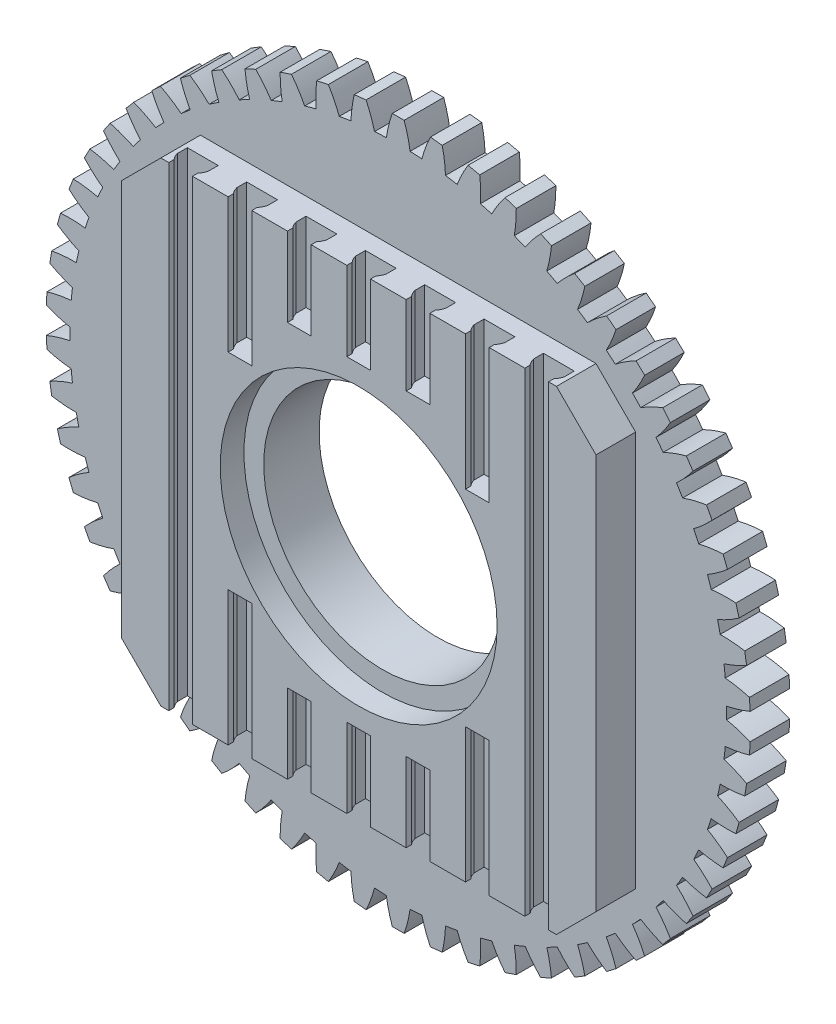
SolidWorks part; units mm, degrees
ref_plane "前视基准面" through (0, 0, 0) normal (0, 0, 1) x (1, 0, 0)
ref_plane "上视基准面" through (0, 0, 0) normal (0, 1, 0) x (1, 0, 0)
ref_plane "右视基准面" through (0, 0, 0) normal (1, 0, 0) x (0, 0, -1)
sketch "草图1" plane through (0, 0, 0) normal (0, 0, 1) x (1, 0, 0)
  circle A0 centre (0, 0) radius 41.5
extrude "凸台-拉伸1" add sketch "草图1" against normal blind 5
sketch "草图2" plane through (0, 0, 0) normal (0, 0, 1) x (1, 0, 0)
  line L1 (-30, 30) -> (30, 30)
  line L2 (-30, 30) -> (-30, -30)
  line L3 (-30, -30) -> (30, -30)
  line L4 (30, 30) -> (30, -30)
extrude "凸台-拉伸2" add sketch "草图2" along normal blind 5
sketch "草图3" plane through (0, -30, 0) normal (0, -1, 0) x (1, 0, 0)
  line L0 (-30, 5) -> (30, 5) construction
  line L1 (-1.5, 5) -> (1.5, 5)
  line L2 (-1.5, 5) -> (-1.5, 4.3229)
  line L3 (6, 5) -> (6, 4.3229)
  line L4 (1.5, 5) -> (1.5, 4.3229)
  line L5 (-1.95, 2.2) -> (1.95, 2.2)
  line L6 (-1.95, 2.2) -> (-1.95, 3.4444)
  line L7 (1.95, 2.2) -> (1.95, 3.4444)
  line L8 (9.45, 2.2) -> (9.45, 3.4444)
  line L9 (9, 5) -> (9, 4.3229)
  line L10 (6, 5) -> (9, 5)
  line L11 (5.55, 2.2) -> (9.45, 2.2)
  line L12 (5.55, 2.2) -> (5.55, 3.4444)
  line L13 (-9, 5) -> (-9, 4.3229)
  line L14 (-5.55, 2.2) -> (-5.55, 3.4444)
  line L15 (-6, 5) -> (-6, 4.3229)
  line L16 (-9, 5) -> (-6, 5)
  line L17 (-9.45, 2.2) -> (-5.55, 2.2)
  line L18 (-9.45, 2.2) -> (-9.45, 3.4444)
  arc A0 (6, 4.3229) -> (5.55, 3.4444) centre (7.5, 3) ccw
  arc A1 (-1.5, 4.3229) -> (-1.95, 3.4444) centre (0, 3) ccw
  arc A2 (1.95, 3.4444) -> (1.5, 4.3229) centre (0, 3) ccw
  arc A3 (9.45, 3.4444) -> (9, 4.3229) centre (7.5, 3) ccw
  arc A4 (-9, 4.3229) -> (-9.45, 3.4444) centre (-7.5, 3) ccw
  arc A5 (-5.55, 3.4444) -> (-6, 4.3229) centre (-7.5, 3) ccw
extrude "切除-拉伸1" cut sketch "草图3" against normal blind 10
extrude "切除-拉伸2" cut sketch "草图3<2>" along normal blind 10 from offset 60 offset against normal yes
sketch "草图3<2>" plane through (0, -30, 0) normal (0, -1, 0) x (1, 0, 0) same geometry as "草图3"
sketch "草图4" plane through (0, -30, 0) normal (0, -1, 0) x (1, 0, 0)
  line L0 (-16.5, 5) -> (-13.5, 5)
  line L3 (-16.5, 5) -> (-16.5, 4.3229)
  line L7 (-16.95, 2.2) -> (-13.05, 2.2)
  line L9 (-13.5, 5) -> (-13.5, 4.3229)
  line L10 (-16.95, 2.2) -> (-16.95, 3.4444)
  line L11 (-13.05, 2.2) -> (-13.05, 3.4444)
  line L12 (13.5, 5) -> (16.5, 5)
  line L13 (13.5, 5) -> (13.5, 4.3229)
  line L14 (13.05, 2.2) -> (16.95, 2.2)
  line L15 (16.5, 5) -> (16.5, 4.3229)
  line L16 (13.05, 2.2) -> (13.05, 3.4444)
  line L17 (16.95, 2.2) -> (16.95, 3.4444)
  arc A2 (-16.5, 4.3229) -> (-16.95, 3.4444) centre (-15, 3) ccw
  arc A3 (-13.05, 3.4444) -> (-13.5, 4.3229) centre (-15, 3) ccw
  arc A4 (13.5, 4.3229) -> (13.05, 3.4444) centre (15, 3) ccw
  arc A5 (16.95, 3.4444) -> (16.5, 4.3229) centre (15, 3) ccw
extrude "切除-拉伸3" cut sketch "草图4" against normal blind 17
extrude "切除-拉伸4" cut sketch "草图4<2>" along normal blind 17 from offset 60 offset against normal yes
sketch "草图4<2>" plane through (0, -30, 0) normal (0, -1, 0) x (1, 0, 0) same geometry as "草图4"
sketch "草图5" plane through (0, -30, 0) normal (0, -1, 0) x (1, 0, 0)
  line L0 (-21, 5) -> (-21, 4.3229)
  line L3 (-24, 5) -> (-21, 5)
  line L7 (-24.45, 2.2) -> (-20.55, 2.2)
  line L9 (-20.55, 2.2) -> (-20.55, 3.4444)
  line L10 (-24.45, 2.2) -> (-24.45, 3.4444)
  line L11 (-24, 5) -> (-24, 4.3229)
  line L12 (24, 5) -> (24, 4.3229)
  line L13 (21, 5) -> (24, 5)
  line L14 (20.55, 2.2) -> (24.45, 2.2)
  line L15 (24.45, 2.2) -> (24.45, 3.4444)
  line L16 (20.55, 2.2) -> (20.55, 3.4444)
  line L17 (21, 5) -> (21, 4.3229)
  arc A2 (-24, 4.3229) -> (-24.45, 3.4444) centre (-22.5, 3) ccw
  arc A3 (-20.55, 3.4444) -> (-21, 4.3229) centre (-22.5, 3) ccw
  arc A4 (21, 4.3229) -> (20.55, 3.4444) centre (22.5, 3) ccw
  arc A5 (24.45, 3.4444) -> (24, 4.3229) centre (22.5, 3) ccw
extrude "切除-拉伸5" cut sketch "草图5" against normal up to next
chamfer "倒角1" distance 5 angle 45 4 edges at (-30, 30, 2.5) (30, 30, 2.5) (30, -30, 2.5) (-30, -30, 2.5)
sketch "草图6" plane through (0, 0, 5) normal (0, 0, 1) x (1, 0, 0)
  circle A0 centre (0, 0) radius 17.5
extrude "切除-拉伸6" cut sketch "草图6" against normal blind 3
sketch "草图7" plane through (0, 0, 2) normal (0, 0, 1) x (1, 0, 0)
  circle A0 centre (0, 0) radius 15
extrude "切除-拉伸7" cut sketch "草图7" against normal through all
sketch "草图9" plane through (0, 0, -5) normal (0, 0, -1) x (-1, 0, 0)
  circle A0 centre (0, 0) radius 19
  circle A1 centre (0, 0) radius 39.5
extrude "切除-拉伸8" cut sketch "草图9" against normal blind 3
sketch "草图8" plane through (0, 0, -5) normal (0, 0, -1) x (-1, 0, 0)
  line L0 (5.5569, 44.158) -> (4.0657, 44.3202)
  line L1 (10.2987, 43.2984) -> (8.8337, 43.6208)
  line L2 (14.9197, 41.9311) -> (13.4982, 42.41)
  line L3 (0.75, 44.5) -> (-0.75, 44.5)
  line L4 (19.3657, 40.0722) -> (18.0044, 40.702)
  line L5 (23.5848, 37.7435) -> (22.2995, 38.5168)
  line L6 (27.5273, 34.9723) -> (26.3332, 35.88)
  line L7 (31.1471, 31.791) -> (30.0581, 32.8226)
  line L8 (34.4018, 28.2371) -> (33.4307, 29.3803)
  line L9 (37.2531, 24.3521) -> (36.4113, 25.5936)
  line L10 (39.6676, 20.1815) -> (38.965, 21.5068)
  line L11 (41.6171, 15.7744) -> (41.0619, 17.1679)
  line L12 (43.0786, 11.1823) -> (42.6773, 12.6277)
  line L13 (44.0351, 6.4592) -> (43.7924, 7.9394)
  line L14 (44.4753, 1.6603) -> (44.3941, 3.1581)
  line L15 (44.3941, -3.1581) -> (44.4753, -1.6603)
  line L16 (43.7924, -7.9394) -> (44.0351, -6.4592)
  line L17 (42.6773, -12.6277) -> (43.0786, -11.1823)
  line L18 (41.0619, -17.1679) -> (41.6171, -15.7744)
  line L19 (38.965, -21.5068) -> (39.6676, -20.1815)
  line L20 (36.4113, -25.5936) -> (37.2531, -24.3521)
  line L21 (33.4307, -29.3803) -> (34.4018, -28.2371)
  line L22 (30.0581, -32.8226) -> (31.1471, -31.791)
  line L23 (26.3332, -35.88) -> (27.5273, -34.9723)
  line L24 (22.2995, -38.5168) -> (23.5848, -37.7435)
  line L25 (18.0044, -40.702) -> (19.3657, -40.0722)
  line L26 (13.4982, -42.41) -> (14.9197, -41.9311)
  line L27 (8.8337, -43.6208) -> (10.2987, -43.2984)
  line L28 (4.0657, -44.3202) -> (5.5569, -44.158)
  line L29 (-0.75, -44.5) -> (0.75, -44.5)
  line L30 (-5.5569, -44.158) -> (-4.0657, -44.3202)
  line L31 (-10.2987, -43.2984) -> (-8.8337, -43.6208)
  line L32 (-14.9197, -41.9311) -> (-13.4982, -42.41)
  line L33 (-19.3657, -40.0722) -> (-18.0044, -40.702)
  line L34 (-23.5848, -37.7435) -> (-22.2995, -38.5168)
  line L35 (-27.5273, -34.9723) -> (-26.3332, -35.88)
  line L36 (-31.1471, -31.791) -> (-30.0581, -32.8226)
  line L37 (-34.4018, -28.2371) -> (-33.4307, -29.3803)
  line L38 (-37.2531, -24.3521) -> (-36.4113, -25.5936)
  line L39 (-39.6676, -20.1815) -> (-38.965, -21.5068)
  line L40 (-41.6171, -15.7744) -> (-41.0619, -17.1679)
  line L41 (-43.0786, -11.1823) -> (-42.6773, -12.6277)
  line L42 (-44.0351, -6.4592) -> (-43.7924, -7.9394)
  line L43 (-44.4753, -1.6603) -> (-44.3941, -3.1581)
  line L44 (-44.3941, 3.1581) -> (-44.4753, 1.6603)
  line L45 (-43.7924, 7.9394) -> (-44.0351, 6.4592)
  line L46 (-42.6773, 12.6277) -> (-43.0786, 11.1823)
  line L47 (-41.0619, 17.1679) -> (-41.6171, 15.7744)
  line L48 (-38.965, 21.5068) -> (-39.6676, 20.1815)
  line L49 (-36.4113, 25.5936) -> (-37.2531, 24.3521)
  line L50 (-33.4307, 29.3803) -> (-34.4018, 28.2371)
  line L51 (-30.0581, 32.8226) -> (-31.1471, 31.791)
  line L52 (-26.3332, 35.88) -> (-27.5273, 34.9723)
  line L53 (-22.2995, 38.5168) -> (-23.5848, 37.7435)
  line L54 (-18.0044, 40.702) -> (-19.3657, 40.0722)
  line L55 (-13.4982, 42.41) -> (-14.9197, 41.9311)
  line L56 (-8.8337, 43.6208) -> (-10.2987, 43.2984)
  line L57 (-4.0657, 44.3202) -> (-5.5569, 44.158)
  arc A0 (1.5, 41.4729) -> (-1.5, 41.4729) centre (0, 0) ccw
  arc A1 (-0.75, 44.5) -> (-1.5, 41.4729) centre (14.3529, 39.1516) ccw
  arc A2 (5.9752, 41.0676) -> (2.9928, 41.3919) centre (0, 0) ccw
  arc A3 (0.75, 44.5) -> (1.5, 41.4729) centre (-14.3529, 39.1516) cw
  arc A4 (4.0657, 44.3202) -> (2.9928, 41.3919) centre (18.5018, 37.3703) ccw
  arc A5 (5.5569, 44.158) -> (5.9752, 41.0676) centre (-10.0357, 40.4739) cw
  arc A6 (10.3804, 40.1808) -> (7.4505, 40.8257) centre (0, 0) ccw
  arc A7 (8.8337, 43.6208) -> (7.4505, 40.8257) centre (22.4338, 35.1508) ccw
  arc A8 (10.2987, 43.2984) -> (10.3804, 40.1808) centre (-5.6009, 41.3217) cw
  arc A9 (14.6638, 38.823) -> (11.8209, 39.7809) centre (0, 0) ccw
  arc A10 (13.4982, 42.41) -> (11.8209, 39.7809) centre (26.1028, 32.5193) ccw
  arc A11 (14.9197, 41.9311) -> (14.6638, 38.823) centre (-1.1004, 41.6851) cw
  arc A12 (18.7754, 37.0099) -> (16.0526, 38.2696) centre (0, 0) ccw
  arc A13 (18.0044, 40.702) -> (16.0526, 38.2696) centre (29.4657, 29.5064) ccw
  arc A14 (19.3657, 40.0722) -> (18.7754, 37.0099) centre (3.413, 41.5597) cw
  arc A15 (22.6668, 34.763) -> (20.0962, 36.3097) centre (0, 0) ccw
  arc A16 (22.2995, 38.5168) -> (20.0962, 36.3097) centre (32.4832, 26.1477) ccw
  arc A17 (23.5848, 37.7435) -> (22.6668, 34.763) centre (7.8864, 40.9471) cw
  arc A18 (26.2925, 32.1085) -> (23.9042, 33.924) centre (0, 0) ccw
  arc A19 (26.3332, 35.88) -> (23.9042, 33.924) centre (35.1198, 22.4823) ccw
  arc A20 (27.5273, 34.9723) -> (26.2925, 32.1085) centre (12.2673, 39.8543) cw
  arc A21 (29.6099, 29.0776) -> (27.4319, 31.1407) centre (0, 0) ccw
  arc A22 (30.0581, 32.8226) -> (27.4319, 31.1407) centre (37.3447, 18.5534) ccw
  arc A23 (31.1471, 31.791) -> (29.6099, 29.0776) centre (16.5044, 38.2944) cw
  arc A24 (32.5801, 25.7057) -> (30.638, 27.9922) centre (0, 0) ccw
  arc A25 (33.4307, 29.3803) -> (30.638, 27.9922) centre (39.1318, 14.407) ccw
  arc A26 (34.4018, 28.2371) -> (32.5801, 25.7057) centre (20.548, 36.2855) cw
  arc A27 (35.1684, 22.0325) -> (33.4849, 24.5156) centre (0, 0) ccw
  arc A28 (36.4113, 25.5936) -> (33.4849, 24.5156) centre (40.46, 10.0916) ccw
  arc A29 (37.2531, 24.3521) -> (35.1684, 22.0325) centre (24.3507, 33.8511) cw
  arc A30 (37.3444, 18.101) -> (35.9392, 20.7515) centre (0, 0) ccw
  arc A31 (38.965, 21.5068) -> (35.9392, 20.7515) centre (41.314, 5.658) ccw
  arc A32 (39.6676, 20.1815) -> (37.3444, 18.101) centre (27.8679, 31.0199) cw
  arc A33 (39.0825, 13.9572) -> (37.9721, 16.7442) centre (0, 0) ccw
  arc A34 (41.0619, 17.1679) -> (37.9721, 16.7442) centre (41.6835, 1.158) ccw
  arc A35 (41.6171, 15.7744) -> (39.0825, 13.9572) centre (31.0584, 27.825) cw
  arc A36 (40.3625, 9.6498) -> (39.5599, 12.5405) centre (0, 0) ccw
  arc A37 (42.6773, 12.6277) -> (39.5599, 12.5405) centre (41.5644, -3.3556) ccw
  arc A38 (43.0786, 11.1823) -> (40.3625, 9.6498) centre (33.8847, 24.3039) cw
  arc A39 (41.1692, 5.2293) -> (40.6839, 8.1898) centre (0, 0) ccw
  arc A40 (43.7924, 7.9394) -> (40.6839, 8.1898) centre (40.9579, -7.8298) ccw
  arc A41 (44.0351, 6.4592) -> (41.1692, 5.2293) centre (36.3138, 20.4979) cw
  arc A42 (41.4933, 0.7475) -> (41.3309, 3.7431) centre (0, 0) ccw
  arc A43 (44.3941, 3.1581) -> (41.3309, 3.7431) centre (39.8713, -12.2122) ccw
  arc A44 (44.4753, 1.6603) -> (41.4933, 0.7475) centre (38.3172, 16.4515) cw
  arc A45 (41.3309, -3.7431) -> (41.4933, -0.7475) centre (0, 0) ccw
  arc A46 (44.4753, -1.6603) -> (41.4933, -0.7475) centre (38.3172, -16.4515) ccw
  arc A47 (44.3941, -3.1581) -> (41.3309, -3.7431) centre (39.8713, 12.2122) cw
  arc A48 (40.6839, -8.1898) -> (41.1692, -5.2293) centre (0, 0) ccw
  arc A49 (44.0351, -6.4592) -> (41.1692, -5.2293) centre (36.3138, -20.4979) ccw
  arc A50 (43.7924, -7.9394) -> (40.6839, -8.1898) centre (40.9579, 7.8298) cw
  arc A51 (39.5599, -12.5405) -> (40.3625, -9.6498) centre (0, 0) ccw
  arc A52 (43.0786, -11.1823) -> (40.3625, -9.6498) centre (33.8847, -24.3039) ccw
  arc A53 (42.6773, -12.6277) -> (39.5599, -12.5405) centre (41.5644, 3.3556) cw
  arc A54 (37.9721, -16.7442) -> (39.0825, -13.9572) centre (0, 0) ccw
  arc A55 (41.6171, -15.7744) -> (39.0825, -13.9572) centre (31.0584, -27.825) ccw
  arc A56 (41.0619, -17.1679) -> (37.9721, -16.7442) centre (41.6835, -1.158) cw
  arc A57 (35.9392, -20.7515) -> (37.3444, -18.101) centre (0, 0) ccw
  arc A58 (39.6676, -20.1815) -> (37.3444, -18.101) centre (27.8679, -31.0199) ccw
  arc A59 (38.965, -21.5068) -> (35.9392, -20.7515) centre (41.314, -5.658) cw
  arc A60 (33.4849, -24.5156) -> (35.1684, -22.0325) centre (0, 0) ccw
  arc A61 (37.2531, -24.3521) -> (35.1684, -22.0325) centre (24.3507, -33.8511) ccw
  arc A62 (36.4113, -25.5936) -> (33.4849, -24.5156) centre (40.46, -10.0916) cw
  arc A63 (30.638, -27.9922) -> (32.5801, -25.7057) centre (0, 0) ccw
  arc A64 (34.4018, -28.2371) -> (32.5801, -25.7057) centre (20.548, -36.2855) ccw
  arc A65 (33.4307, -29.3803) -> (30.638, -27.9922) centre (39.1318, -14.407) cw
  arc A66 (27.4319, -31.1407) -> (29.6099, -29.0776) centre (0, 0) ccw
  arc A67 (31.1471, -31.791) -> (29.6099, -29.0776) centre (16.5044, -38.2944) ccw
  arc A68 (30.0581, -32.8226) -> (27.4319, -31.1407) centre (37.3447, -18.5534) cw
  arc A69 (23.9042, -33.924) -> (26.2925, -32.1085) centre (0, 0) ccw
  arc A70 (27.5273, -34.9723) -> (26.2925, -32.1085) centre (12.2673, -39.8543) ccw
  arc A71 (26.3332, -35.88) -> (23.9042, -33.924) centre (35.1198, -22.4823) cw
  arc A72 (20.0962, -36.3097) -> (22.6668, -34.763) centre (0, 0) ccw
  arc A73 (23.5848, -37.7435) -> (22.6668, -34.763) centre (7.8864, -40.9471) ccw
  arc A74 (22.2995, -38.5168) -> (20.0962, -36.3097) centre (32.4832, -26.1477) cw
  arc A75 (16.0526, -38.2696) -> (18.7754, -37.0099) centre (0, 0) ccw
  arc A76 (19.3657, -40.0722) -> (18.7754, -37.0099) centre (3.413, -41.5597) ccw
  arc A77 (18.0044, -40.702) -> (16.0526, -38.2696) centre (29.4657, -29.5064) cw
  arc A78 (11.8209, -39.7809) -> (14.6638, -38.823) centre (0, 0) ccw
  arc A79 (14.9197, -41.9311) -> (14.6638, -38.823) centre (-1.1004, -41.6851) ccw
  arc A80 (13.4982, -42.41) -> (11.8209, -39.7809) centre (26.1028, -32.5193) cw
  arc A81 (7.4505, -40.8257) -> (10.3804, -40.1808) centre (0, 0) ccw
  arc A82 (10.2987, -43.2984) -> (10.3804, -40.1808) centre (-5.6009, -41.3217) ccw
  arc A83 (8.8337, -43.6208) -> (7.4505, -40.8257) centre (22.4338, -35.1508) cw
  arc A84 (2.9928, -41.3919) -> (5.9752, -41.0676) centre (0, 0) ccw
  arc A85 (5.5569, -44.158) -> (5.9752, -41.0676) centre (-10.0357, -40.4739) ccw
  arc A86 (4.0657, -44.3202) -> (2.9928, -41.3919) centre (18.5018, -37.3703) cw
  arc A87 (-1.5, -41.4729) -> (1.5, -41.4729) centre (0, 0) ccw
  arc A88 (0.75, -44.5) -> (1.5, -41.4729) centre (-14.3529, -39.1516) ccw
  arc A89 (-0.75, -44.5) -> (-1.5, -41.4729) centre (14.3529, -39.1516) cw
  arc A90 (-5.9752, -41.0676) -> (-2.9928, -41.3919) centre (0, 0) ccw
  arc A91 (-4.0657, -44.3202) -> (-2.9928, -41.3919) centre (-18.5018, -37.3703) ccw
  arc A92 (-5.5569, -44.158) -> (-5.9752, -41.0676) centre (10.0357, -40.4739) cw
  arc A93 (-10.3804, -40.1808) -> (-7.4505, -40.8257) centre (0, 0) ccw
  arc A94 (-8.8337, -43.6208) -> (-7.4505, -40.8257) centre (-22.4338, -35.1508) ccw
  arc A95 (-10.2987, -43.2984) -> (-10.3804, -40.1808) centre (5.6009, -41.3217) cw
  arc A96 (-14.6638, -38.823) -> (-11.8209, -39.7809) centre (0, 0) ccw
  arc A97 (-13.4982, -42.41) -> (-11.8209, -39.7809) centre (-26.1028, -32.5193) ccw
  arc A98 (-14.9197, -41.9311) -> (-14.6638, -38.823) centre (1.1004, -41.6851) cw
  arc A99 (-18.7754, -37.0099) -> (-16.0526, -38.2696) centre (0, 0) ccw
  arc A100 (-18.0044, -40.702) -> (-16.0526, -38.2696) centre (-29.4657, -29.5064) ccw
  arc A101 (-19.3657, -40.0722) -> (-18.7754, -37.0099) centre (-3.413, -41.5597) cw
  arc A102 (-22.6668, -34.763) -> (-20.0962, -36.3097) centre (0, 0) ccw
  arc A103 (-22.2995, -38.5168) -> (-20.0962, -36.3097) centre (-32.4832, -26.1477) ccw
  arc A104 (-23.5848, -37.7435) -> (-22.6668, -34.763) centre (-7.8864, -40.9471) cw
  arc A105 (-26.2925, -32.1085) -> (-23.9042, -33.924) centre (0, 0) ccw
  arc A106 (-26.3332, -35.88) -> (-23.9042, -33.924) centre (-35.1198, -22.4823) ccw
  arc A107 (-27.5273, -34.9723) -> (-26.2925, -32.1085) centre (-12.2673, -39.8543) cw
  arc A108 (-29.6099, -29.0776) -> (-27.4319, -31.1407) centre (0, 0) ccw
  arc A109 (-30.0581, -32.8226) -> (-27.4319, -31.1407) centre (-37.3447, -18.5534) ccw
  arc A110 (-31.1471, -31.791) -> (-29.6099, -29.0776) centre (-16.5044, -38.2944) cw
  arc A111 (-32.5801, -25.7057) -> (-30.638, -27.9922) centre (0, 0) ccw
  arc A112 (-33.4307, -29.3803) -> (-30.638, -27.9922) centre (-39.1318, -14.407) ccw
  arc A113 (-34.4018, -28.2371) -> (-32.5801, -25.7057) centre (-20.548, -36.2855) cw
  arc A114 (-35.1684, -22.0325) -> (-33.4849, -24.5156) centre (0, 0) ccw
  arc A115 (-36.4113, -25.5936) -> (-33.4849, -24.5156) centre (-40.46, -10.0916) ccw
  arc A116 (-37.2531, -24.3521) -> (-35.1684, -22.0325) centre (-24.3507, -33.8511) cw
  arc A117 (-37.3444, -18.101) -> (-35.9392, -20.7515) centre (0, 0) ccw
  arc A118 (-38.965, -21.5068) -> (-35.9392, -20.7515) centre (-41.314, -5.658) ccw
  arc A119 (-39.6676, -20.1815) -> (-37.3444, -18.101) centre (-27.8679, -31.0199) cw
  arc A120 (-39.0825, -13.9572) -> (-37.9721, -16.7442) centre (0, 0) ccw
  arc A121 (-41.0619, -17.1679) -> (-37.9721, -16.7442) centre (-41.6835, -1.158) ccw
  arc A122 (-41.6171, -15.7744) -> (-39.0825, -13.9572) centre (-31.0584, -27.825) cw
  arc A123 (-40.3625, -9.6498) -> (-39.5599, -12.5405) centre (0, 0) ccw
  arc A124 (-42.6773, -12.6277) -> (-39.5599, -12.5405) centre (-41.5644, 3.3556) ccw
  arc A125 (-43.0786, -11.1823) -> (-40.3625, -9.6498) centre (-33.8847, -24.3039) cw
  arc A126 (-41.1692, -5.2293) -> (-40.6839, -8.1898) centre (0, 0) ccw
  arc A127 (-43.7924, -7.9394) -> (-40.6839, -8.1898) centre (-40.9579, 7.8298) ccw
  arc A128 (-44.0351, -6.4592) -> (-41.1692, -5.2293) centre (-36.3138, -20.4979) cw
  arc A129 (-41.4933, -0.7475) -> (-41.3309, -3.7431) centre (0, 0) ccw
  arc A130 (-44.3941, -3.1581) -> (-41.3309, -3.7431) centre (-39.8713, 12.2122) ccw
  arc A131 (-44.4753, -1.6603) -> (-41.4933, -0.7475) centre (-38.3172, -16.4515) cw
  arc A132 (-41.3309, 3.7431) -> (-41.4933, 0.7475) centre (0, 0) ccw
  arc A133 (-44.4753, 1.6603) -> (-41.4933, 0.7475) centre (-38.3172, 16.4515) ccw
  arc A134 (-44.3941, 3.1581) -> (-41.3309, 3.7431) centre (-39.8713, -12.2122) cw
  arc A135 (-40.6839, 8.1898) -> (-41.1692, 5.2293) centre (0, 0) ccw
  arc A136 (-44.0351, 6.4592) -> (-41.1692, 5.2293) centre (-36.3138, 20.4979) ccw
  arc A137 (-43.7924, 7.9394) -> (-40.6839, 8.1898) centre (-40.9579, -7.8298) cw
  arc A138 (-39.5599, 12.5405) -> (-40.3625, 9.6498) centre (0, 0) ccw
  arc A139 (-43.0786, 11.1823) -> (-40.3625, 9.6498) centre (-33.8847, 24.3039) ccw
  arc A140 (-42.6773, 12.6277) -> (-39.5599, 12.5405) centre (-41.5644, -3.3556) cw
  arc A141 (-37.9721, 16.7442) -> (-39.0825, 13.9572) centre (0, 0) ccw
  arc A142 (-41.6171, 15.7744) -> (-39.0825, 13.9572) centre (-31.0584, 27.825) ccw
  arc A143 (-41.0619, 17.1679) -> (-37.9721, 16.7442) centre (-41.6835, 1.158) cw
  arc A144 (-35.9392, 20.7515) -> (-37.3444, 18.101) centre (0, 0) ccw
  arc A145 (-39.6676, 20.1815) -> (-37.3444, 18.101) centre (-27.8679, 31.0199) ccw
  arc A146 (-38.965, 21.5068) -> (-35.9392, 20.7515) centre (-41.314, 5.658) cw
  arc A147 (-33.4849, 24.5156) -> (-35.1684, 22.0325) centre (0, 0) ccw
  arc A148 (-37.2531, 24.3521) -> (-35.1684, 22.0325) centre (-24.3507, 33.8511) ccw
  arc A149 (-36.4113, 25.5936) -> (-33.4849, 24.5156) centre (-40.46, 10.0916) cw
  arc A150 (-30.638, 27.9922) -> (-32.5801, 25.7057) centre (0, 0) ccw
  arc A151 (-34.4018, 28.2371) -> (-32.5801, 25.7057) centre (-20.548, 36.2855) ccw
  arc A152 (-33.4307, 29.3803) -> (-30.638, 27.9922) centre (-39.1318, 14.407) cw
  arc A153 (-27.4319, 31.1407) -> (-29.6099, 29.0776) centre (0, 0) ccw
  arc A154 (-31.1471, 31.791) -> (-29.6099, 29.0776) centre (-16.5044, 38.2944) ccw
  arc A155 (-30.0581, 32.8226) -> (-27.4319, 31.1407) centre (-37.3447, 18.5534) cw
  arc A156 (-23.9042, 33.924) -> (-26.2925, 32.1085) centre (0, 0) ccw
  arc A157 (-27.5273, 34.9723) -> (-26.2925, 32.1085) centre (-12.2673, 39.8543) ccw
  arc A158 (-26.3332, 35.88) -> (-23.9042, 33.924) centre (-35.1198, 22.4823) cw
  arc A159 (-20.0962, 36.3097) -> (-22.6668, 34.763) centre (0, 0) ccw
  arc A160 (-23.5848, 37.7435) -> (-22.6668, 34.763) centre (-7.8864, 40.9471) ccw
  arc A161 (-22.2995, 38.5168) -> (-20.0962, 36.3097) centre (-32.4832, 26.1477) cw
  arc A162 (-16.0526, 38.2696) -> (-18.7754, 37.0099) centre (0, 0) ccw
  arc A163 (-19.3657, 40.0722) -> (-18.7754, 37.0099) centre (-3.413, 41.5597) ccw
  arc A164 (-18.0044, 40.702) -> (-16.0526, 38.2696) centre (-29.4657, 29.5064) cw
  arc A165 (-11.8209, 39.7809) -> (-14.6638, 38.823) centre (0, 0) ccw
  arc A166 (-14.9197, 41.9311) -> (-14.6638, 38.823) centre (1.1004, 41.6851) ccw
  arc A167 (-13.4982, 42.41) -> (-11.8209, 39.7809) centre (-26.1028, 32.5193) cw
  arc A168 (-7.4505, 40.8257) -> (-10.3804, 40.1808) centre (0, 0) ccw
  arc A169 (-10.2987, 43.2984) -> (-10.3804, 40.1808) centre (5.6009, 41.3217) ccw
  arc A170 (-8.8337, 43.6208) -> (-7.4505, 40.8257) centre (-22.4338, 35.1508) cw
  arc A171 (-2.9928, 41.3919) -> (-5.9752, 41.0676) centre (0, 0) ccw
  arc A172 (-5.5569, 44.158) -> (-5.9752, 41.0676) centre (10.0357, 40.4739) ccw
  arc A173 (-4.0657, 44.3202) -> (-2.9928, 41.3919) centre (-18.5018, 37.3703) cw
  dimension "D1" = 58
extrude "凸台-拉伸3" add sketch "草图8" against normal up to surface (5 mm away) up to face at (41.5, 0, 0)
